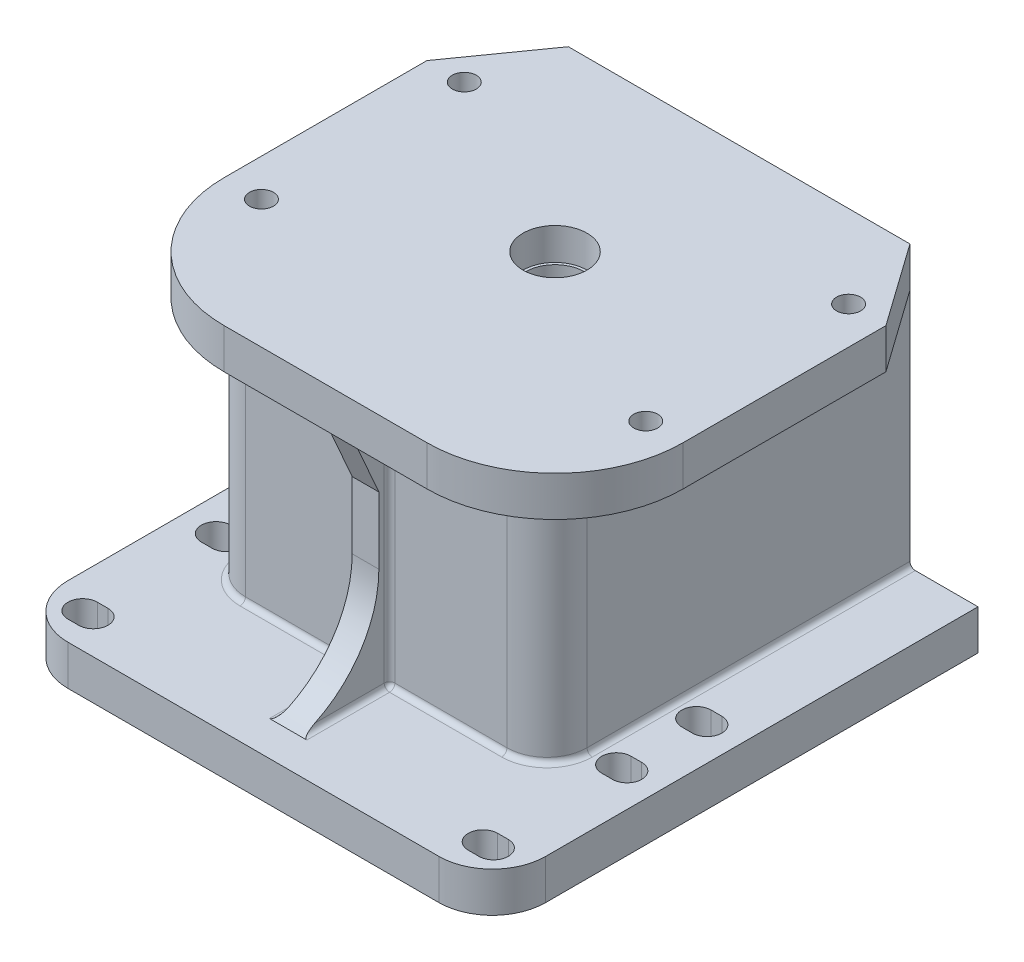
SolidWorks part; units mm, degrees
ref_plane "前视基准面" through (0, 0, 0) normal (0, 0, 1) x (1, 0, 0)
ref_plane "上视基准面" through (0, 0, 0) normal (0, 1, 0) x (1, 0, 0)
ref_plane "右视基准面" through (0, 0, 0) normal (1, 0, 0) x (0, 0, -1)
sketch "草图1" plane through (0, 0, 0) normal (0, 1, 0) x (1, 0, 0)
  line L0 (0, 0) -> (0, 57.2406) construction
  line L1 (-89.5, 91) -> (89.5, 91)
  line L2 (-89.5, 91) -> (-89.5, -91)
  line L3 (-89.5, -91) -> (89.5, -91)
  line L4 (89.5, 91) -> (89.5, -91)
  line L5 (0, 0) -> (97.114, 0) construction
  dimension "D1" = 179
  dimension "D2" = 182
extrude "凸台-拉伸1" add sketch "草图1" along normal blind 15
sketch "草图2" plane through (0, 15, 0) normal (0, 1, 0) x (1, 0, 0)
  line L1 (89.5, 91) -> (-89.5, 91) construction
  circle A0 centre (0, 22) radius 15
  dimension "D1" = 30
  dimension "D2" = 69
extrude "切除-拉伸1" cut sketch "草图2" against normal through all
sketch "草图4" plane through (0, 15, 0) normal (0, 1, 0) x (1, 0, 0)
  line L0 (-77, -78) -> (-73, -78) construction
  line L1 (-77, -72.5) -> (-73, -72.5)
  line L2 (-77, -83.5) -> (-73, -83.5)
  line L3 (-77, -28) -> (-73, -28) construction
  line L4 (-77, -22.5) -> (-73, -22.5)
  line L5 (-77, -33.5) -> (-73, -33.5)
  line L6 (-77, 2) -> (-73, 2) construction
  line L7 (-77, 7.5) -> (-73, 7.5)
  line L8 (-77, -3.5) -> (-73, -3.5)
  line L9 (0, 0) -> (0, -115.7531) construction
  line L10 (77, 2) -> (73, 2) construction
  line L11 (77, 7.5) -> (73, 7.5)
  line L12 (77, -3.5) -> (73, -3.5)
  line L13 (77, -28) -> (73, -28) construction
  line L14 (77, -22.5) -> (73, -22.5)
  line L15 (77, -33.5) -> (73, -33.5)
  line L16 (77, -78) -> (73, -78) construction
  line L17 (77, -72.5) -> (73, -72.5)
  line L18 (77, -83.5) -> (73, -83.5)
  line L19 (-89.5, -91) -> (89.5, -91) construction
  arc A0 (-77, -72.5) -> (-77, -83.5) centre (-77, -78) ccw
  arc A1 (-73, -83.5) -> (-73, -72.5) centre (-73, -78) ccw
  arc A2 (-77, -22.5) -> (-77, -33.5) centre (-77, -28) ccw
  arc A3 (-73, -33.5) -> (-73, -22.5) centre (-73, -28) ccw
  arc A4 (-77, 7.5) -> (-77, -3.5) centre (-77, 2) ccw
  arc A5 (-73, -3.5) -> (-73, 7.5) centre (-73, 2) ccw
  arc A6 (77, 7.5) -> (77, -3.5) centre (77, 2) cw
  arc A7 (73, -3.5) -> (73, 7.5) centre (73, 2) cw
  arc A8 (77, -22.5) -> (77, -33.5) centre (77, -28) cw
  arc A9 (73, -33.5) -> (73, -22.5) centre (73, -28) cw
  arc A10 (77, -72.5) -> (77, -83.5) centre (77, -78) cw
  arc A11 (73, -83.5) -> (73, -72.5) centre (73, -78) cw
  point P2 (-75, -78)
  point P7 (-75, -28)
  point P14 (-75, 2)
  point P26 (75, 2)
  point P33 (75, -28)
  point P40 (75, -78)
  dimension "D6" = 5.5
  dimension "D1" = 150
  dimension "D2" = 4
  dimension "D3" = 13
  dimension "D4" = 50
  dimension "D5" = 30
extrude "切除-拉伸3" cut sketch "草图4" against normal through all
fillet "圆角1" radius 20 2 edges at (-89.5, 7.5, 91) (89.5, 7.5, 91)
sketch "草图5" plane through (0, 15, 0) normal (0, 1, 0) x (1, 0, 0)
  line L0 (-64, 91) -> (-64, -45)
  line L1 (89.5, 91) -> (-89.5, 91) construction
  line L2 (-64, -45) -> (64, -45)
  line L3 (64, -45) -> (64, 91)
  line L4 (64, 91) -> (39, 91)
  line L5 (39, 91) -> (39, -29)
  line L6 (39, -29) -> (-39, -29)
  line L7 (-39, -29) -> (-39, 91)
  line L8 (-39, 91) -> (-64, 91)
  line L9 (0, 0) -> (0, 72.5369) construction
  dimension "D1" = 25
  dimension "D2" = 128
  dimension "D3" = 16
  dimension "D4" = 136
extrude "凸台-拉伸2" add sketch "草图5" along normal blind 90
fillet "圆角2" radius 15 2 edges at (64, 60, 45) (-64, 60, 45)
sketch "草图6" plane through (0, 0, 0) normal (1, 0, 0) x (0, 0, -1)
  line L0 (-45, 105) -> (-60, 105)
  line L1 (-45, 15) -> (-78, 15)
  line L2 (-71, 15) -> (-91, 15) construction
  line L3 (-49, 80) -> (-49, 54.9375)
  line L4 (-45, 15) -> (-45, 105) construction
  line L5 (-60, 105) -> (-49, 80)
  line L6 (-45, 105) -> (-45, 15)
  arc A0 (-78, 15) -> (-49, 54.9375) centre (-91, 54.9375) ccw
  dimension "D5" = 84
  dimension "D1" = 4
  dimension "D2" = 33
  dimension "D3" = 15
  dimension "D4" = 25
extrude "凸台-拉伸3" add sketch "草图6" along normal mid plane 10
sketch "草图7" plane through (0, 105, 0) normal (0, 1, 0) x (1, 0, 0)
  line L0 (-64, 91) -> (-89.5, 91) construction
  line L1 (-86, 91) -> (86, 91)
  line L2 (-86, 91) -> (-86, -64)
  line L3 (-86, -64) -> (86, -64)
  line L4 (86, 91) -> (86, -64)
  line L5 (0, 0) -> (0, 128.3555) construction
  dimension "D1" = 172
  dimension "D2" = 155
extrude "凸台-拉伸4" add sketch "草图7" along normal blind 15
sketch "草图8" plane through (0, 120, 0) normal (0, 1, 0) x (1, 0, 0)
  line L0 (-86, 91) -> (-86, 60)
  line L1 (-86, 91) -> (-86, -64) construction
  line L2 (-86, 60) -> (-64, 91)
  line L3 (-64, 91) -> (-89.5, 91) construction
  line L4 (-64, 91) -> (-86, 91)
  line L5 (0, 0) -> (0, 119.7507) construction
  line L6 (64, 91) -> (86, 91)
  line L7 (86, 60) -> (64, 91)
  line L8 (86, 91) -> (86, 60)
  dimension "D1" = 22
  dimension "D2" = 31
extrude "切除-拉伸4" cut sketch "草图8" against normal up to surface (15 mm away) up to face at (1.5714, 105, 9.3009)
fillet "圆角3" radius 48 2 edges at (86, 112.5, 64) (-86, 112.5, 64)
sketch "草图9" plane through (0, 120, 0) normal (0, 1, 0) x (1, 0, 0)
  line L0 (0, 0) -> (0, 126.4912) construction
  line L1 (64, 91) -> (-64, 91) construction
  circle A0 centre (-72, 60) radius 4.5
  circle A1 centre (-72, -16) radius 4.5
  circle A2 centre (72, -16) radius 4.5
  circle A3 centre (72, 60) radius 4.5
  dimension "D4" = 9
  dimension "D1" = 144
  dimension "D2" = 31
  dimension "D3" = 76
extrude "切除-拉伸5" cut sketch "草图9" against normal up to surface (15 mm away) up to face at (1.375, 105, 15.256)
sketch "草图11" plane through (0, 0, 0) normal (1, 0, 0) x (0, 0, -1)
  line L0 (-29, 105) -> (-29, 102)
  line L1 (-29, 105) -> (-29, 15) construction
  line L2 (-29, 102) -> (40, 102)
  line L3 (40, 102) -> (40, 105)
  line L4 (60, 105) -> (91, 105) construction
  line L5 (40, 105) -> (-29, 105)
  dimension "D1" = 69
  dimension "D2" = 3
extrude "凸台-拉伸5" add sketch "草图11" along normal mid plane 36
fillet "圆角4" radius 18 2 edges at (-18, 103.5, -40) (18, 103.5, -40)
sketch "草图12" plane through (0, 120, 0) normal (0, 1, 0) x (1, 0, 0)
  line L0 (64, 91) -> (-64, 91) construction
  circle A0 centre (0, 22) radius 12
  dimension "D1" = 24
  dimension "D2" = 69
extrude "切除-拉伸6" cut sketch "草图12" against normal blind 12
sketch "草图13" plane through (0, 108, 0) normal (0, 1, 0) x (1, 0, 0)
  circle A0 centre (0, 22) radius 11
  dimension "D1" = 22
extrude "切除-拉伸7" cut sketch "草图13" against normal up to surface (6 mm away) up to face at (0, 102, -6.6912)
fillet "圆角5" radius 2 12 edges at (-64, 15, -30.5) (-59.6066, 15, 40.6066) (64, 15, -30.5) (59.6066, 15, 40.6066) (5, 105, 52.5) (-5, 105, 52.5) (-5, 60, 45) (5, 60, 45) (-5, 15, 61.5) (5, 15, 61.5) (-27, 15, 45) (27, 15, 45)
